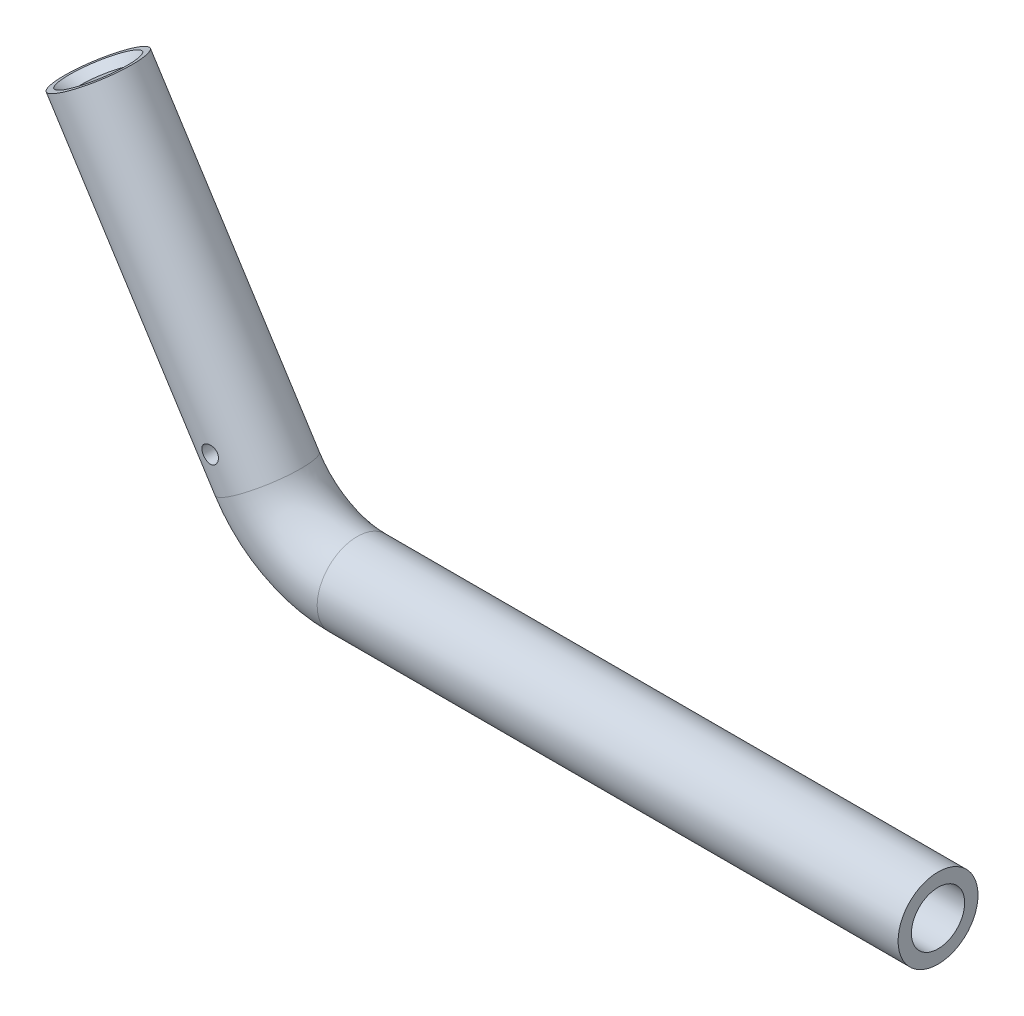
SolidWorks part; units mm, degrees
material "6061-T6 (SS)"
ref_plane "Front Plane" through (0, 0, 0) normal (0, 0, 1) x (1, 0, 0)
ref_plane "Top Plane" through (0, 0, 0) normal (0, 1, 0) x (1, 0, 0)
ref_plane "Right Plane" through (0, 0, 0) normal (1, 0, 0) x (0, 0, -1)
sketch "Sketch1" plane through (0, 0, 0) normal (0, 0, 1) x (1, 0, 0)
  line L0 (27.8698, 0) -> (304.8, 0)
  line L1 (-14.9745, 23.5052) -> (-95.5319, 149.955)
  arc A0 (-14.9745, 23.5052) -> (27.8698, 0) centre (27.8698, 50.8) ccw
  point P7 (0, 0)
  dimension "D4" = 50.8
  dimension "D1" = 122.5
  dimension "D2" = 304.8
  dimension "D3" = 177.8
sweep "Sweep1" add path "Sketch1" circular profile diameter 38.1 parameters "D3"=38.1
sweep "Cut-Sweep1" cut path "Sketch1<2>" circular profile diameter 25.4 parameters "D3"=25.4
sketch "Sketch1<2>" plane through (0, 0, 0) normal (0, 0, 1) x (1, 0, 0) same geometry as "Sketch1"
sketch "Sketch46" plane through (0, 0, 0) normal (0, 0, 1) x (1, 0, 0)
  line L0 (1.0922, 33.7407) -> (-31.0411, 13.2696) construction
  line L1 (-79.4653, 160.1906) -> (-111.5985, 139.7194) construction
  line L2 (1.0922, 33.7407) -> (-31.0411, 13.2696) construction
  line L3 (-79.4653, 160.1906) -> (-111.5985, 139.7194) construction
  line L4 (-79.4653, 160.1906) -> (1.0922, 33.7407) construction
  line L5 (-111.5985, 139.7194) -> (-31.0411, 13.2696) construction
  line L7 (-23.4358, 36.7869) -> (-14.9745, 23.5052) construction
  circle A0 centre (-23.4358, 36.7869) radius 3.937
  dimension "D1" = 7.874
  dimension "D2" = 15.748
extrude "Cut-Extrude1" cut sketch "Sketch46" against normal through all both and the other way through all
sketch "Sketch47" plane through (0, 0, 0) normal (0, 0, 1) x (1, 0, 0)
  line L0 (27.8698, 0) -> (304.8, 0) construction
  line L1 (304.8, -19.05) -> (304.8, 19.05) construction
  line L2 (27.8698, 19.05) -> (27.8698, -19.05) construction
  line L3 (304.8, -19.05) -> (304.8, 19.05) construction
  line L4 (27.8698, 19.05) -> (27.8698, -19.05) construction
  line L5 (27.8698, -19.05) -> (304.8, -19.05) construction
  line L6 (159.6571, 0) -> (159.6571, -19.05) construction
  point P0 (159.6571, 0)
  dimension "D1" = 145.1429
ref_point "Point1"
chamfer "Chamfer3" distance 3.556 angle 50 1 edges at (-84.8208, 156.7787, 0) first distance on face at (-84.8208, 156.7787, 0)
equation "\"D2@Sketch1\"=\"extension_length\""
equation "\"tilt_angle\"= 122.5deg"
equation "\"extension_length\"= 12in"
equation "\"reciever_length\"= 7in"
equation "\"D1@Sketch1\"=\"tilt_angle\""
equation "\"D3@Sketch1\"=\"reciever_length\""
equation "\"tilt_radius\"= 2in"
equation "\"D4@Sketch1\"=\"tilt_radius\""
equation "\"reciever_inner_dia\"= 1in"
equation "\"reciever_thickness\"= 0.25in"
equation "\"reciever_outer_dia\"= \"reciever_inner_dia\" + 2 * \"reciever_thickness\""
equation "\"D3@Sweep1\"=\"reciever_outer_dia\""
equation "\"D3@Cut-Sweep1\"=\"reciever_inner_dia\""
equation "\"pin_dia\"= 0.31in"
equation "\"D1@Sketch46\"=\"pin_dia\""
equation "\"D2@Sketch46\"=2*\"pin_dia\""
equation "\"D1@Sketch47\"=\"extension_length\"/2.1"
